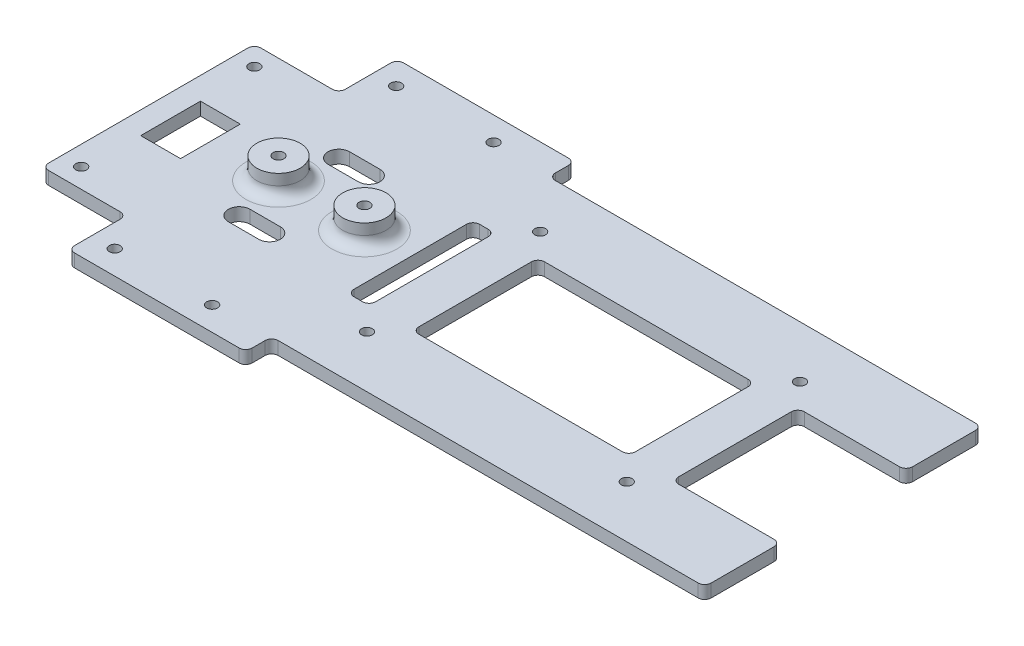
SolidWorks part; units mm, degrees
ref_plane "Front Plane" through (0, 0, 0) normal (0, 0, 1) x (1, 0, 0)
ref_plane "Top Plane" through (0, 0, 0) normal (0, 1, 0) x (1, 0, 0)
ref_plane "Right Plane" through (0, 0, 0) normal (1, 0, 0) x (0, 0, -1)
sketch "Sketch1" plane through (0, 0, 0) normal (0, 1, 0) x (1, 0, 0)
  line L1 (-20.5, -38) -> (20.5, -38)
  line L2 (20.5, -38) -> (20.5, -32)
  line L3 (20.5, -32) -> (120.5, -32)
  line L4 (120.5, -32) -> (120.5, 32)
  line L5 (120.5, 32) -> (20.5, 32)
  line L6 (20.5, 32) -> (20.5, 38)
  line L7 (20.5, 38) -> (-20.5, 38)
  line L8 (-20.5, -24.5) -> (-20.5, -38)
  line L21 (-20.5, 24.5) -> (-20.5, 38)
  line L24 (-40, 24.5) -> (-20.5, 24.5)
  line L26 (-40, 24.5) -> (-40, -24.5)
  line L27 (-40, -24.5) -> (-20.5, -24.5)
  line L28 (-35.5, -20) -> (-35.5, 20) construction
  line L29 (-31, -24.5) -> (-31, 24.5) construction
  circle A0 centre (-35.5, 20) radius 1.25
  circle A1 centre (-35.5, -20) radius 1.25
  point P2 (0, 38)
  point P3 (-40, 0)
  point P22 (-35.5, 0)
  dimension "D7" = 4.5
  dimension "D5" = 4.5
  dimension "D10" = 2.5
  dimension "D1" = 41
  dimension "D2" = 100
  dimension "D3" = 64
  dimension "D4" = 76
  dimension "D6" = 40
  dimension "D8" = 9
  dimension "D9" = 10.5
extrude "Boss-Extrude1" add sketch "Sketch1" along normal blind 3
sketch "Sketch2" plane through (0, 3, 0) normal (0, 1, 0) x (1, 0, 0)
  line L0 (9.925, 0) -> (-9.925, 0) construction
  line L1 (-9.925, 20) -> (-9.925, -20) construction
  line L2 (9.925, 20) -> (9.925, -20) construction
  circle A0 centre (-9.925, 20) radius 5
  circle A1 centre (9.925, 20) radius 5
  circle A2 centre (-9.925, 0) radius 5
  circle A3 centre (9.925, 0) radius 5
  circle A4 centre (9.925, -20) radius 5
  circle A5 centre (-9.925, -20) radius 5
  point P16 (0, 0)
  point P22 (-9.925, 0)
  point P23 (9.925, 0)
  dimension "D2" = 10
  dimension "D1" = 19.85
  dimension "D3" = 40
extrude "Boss-Extrude2" add sketch "Sketch2" along normal blind 5 contours A2 | A3
fillet "Fillet1" radius 2.5 2 edges at (9.925, 3, 5) (-9.925, 3, 5)
sketch "Sketch3" plane through (0, 0, 0) normal (0, -1, 0) x (-1, 0, 0)
  line L0 (9.925, 0) -> (-9.925, 0) construction
  line L1 (-90.5, 20) -> (-30.5, -20) construction
  line L2 (-30.5, 20) -> (-90.5, -20) construction
  line L3 (20.5, -38) -> (-20.5, -38) construction
  line L4 (-7.25, -32.5) -> (15.25, -32.5) construction
  line L7 (-7.25, 32.5) -> (15.25, 32.5) construction
  line L13 (-25.5, 14.5) -> (-20.5, 14.5)
  line L16 (-7.25, 32.5) -> (15.25, -32.5) construction
  line L17 (-25.5, 14.5) -> (-25.5, -14.5)
  line L18 (7.5, 11.5) -> (0.5, 11.5) construction
  line L19 (7.5, 9) -> (0.5, 9)
  line L20 (7.5, 14) -> (0.5, 14)
  line L21 (7.5, -11.5) -> (0.5, -11.5) construction
  line L22 (7.5, -14) -> (0.5, -14)
  line L23 (7.5, -9) -> (0.5, -9)
  line L24 (4, -11.5) -> (4, 11.5) construction
  line L25 (-25.5, -14.5) -> (-20.5, -14.5)
  line L26 (-20.5, 14.5) -> (-20.5, -14.5)
  line L27 (-25.5, 14.5) -> (-20.5, -14.5) construction
  line L28 (-25.5, -14.5) -> (-20.5, 14.5) construction
  line L29 (-120.5, -32) -> (-120.5, 32) construction
  line L30 (-20.5, 32) -> (-20.5, 38) construction
  line L31 (25.65, 6.9) -> (34.85, 6.9)
  line L32 (25.65, 6.9) -> (25.65, -6.9)
  line L33 (25.65, -6.9) -> (34.85, -6.9)
  line L34 (34.85, 6.9) -> (34.85, -6.9)
  line L35 (25.65, 6.9) -> (34.85, -6.9) construction
  line L36 (25.65, -6.9) -> (34.85, 6.9) construction
  line L37 (-120.5, 14.5) -> (-95.5, 14.5)
  line L38 (-120.5, 14.5) -> (-120.5, -14.5)
  line L39 (-120.5, -14.5) -> (-95.5, -14.5)
  line L40 (-95.5, 14.5) -> (-95.5, -14.5)
  line L41 (-120.5, 14.5) -> (-95.5, -14.5) construction
  line L42 (-120.5, -14.5) -> (-95.5, 14.5) construction
  line L43 (40, -24.5) -> (20.5, -24.5) construction
  line L44 (-85.5, 14.5) -> (-35.5, 14.5)
  line L46 (15.25, 32.5) -> (-7.25, -32.5) construction
  line L47 (-85.5, 14.5) -> (-85.5, -14.5)
  line L48 (-85.5, -14.5) -> (-35.5, -14.5)
  line L49 (-35.5, 14.5) -> (-35.5, -14.5)
  line L50 (-85.5, 14.5) -> (-35.5, -14.5) construction
  line L51 (-85.5, -14.5) -> (-35.5, 14.5) construction
  circle A2 centre (-30.5, -20) radius 1.25
  circle A3 centre (-90.5, -20) radius 1.25
  circle A4 centre (-30.5, 20) radius 1.25
  circle A5 centre (-90.5, 20) radius 1.25
  arc A14 (7.5, 9) -> (7.5, 14) centre (7.5, 11.5) ccw
  arc A15 (0.5, 14) -> (0.5, 9) centre (0.5, 11.5) ccw
  arc A16 (7.5, -14) -> (7.5, -9) centre (7.5, -11.5) ccw
  arc A17 (0.5, -9) -> (0.5, -14) centre (0.5, -11.5) ccw
  circle A18 centre (-7.25, 32.5) radius 1.25
  circle A19 centre (15.25, 32.5) radius 1.25
  circle A20 centre (-9.925, 0) radius 1.25
  circle A21 centre (9.925, 0) radius 1.25
  circle A22 centre (15.25, -32.5) radius 1.25
  circle A23 centre (-7.25, -32.5) radius 1.25
  point P8 (0, 0)
  point P16 (-60.5, 0)
  point P17 (-60.5, 0)
  point P25 (4, -32.5)
  point P26 (4, 32.5)
  point P28 (4, 0)
  point P29 (4, 0)
  point P30 (4, 0)
  point P33 (-23, 0)
  point P34 (0, 0)
  point P47 (4, 11.5)
  point P53 (0, 0)
  point P54 (0, 0)
  point P62 (4, -11.5)
  point P69 (10, -11.5)
  point P70 (-2, -11.5)
  point P75 (0, 0)
  point P89 (30.25, 0)
  point P93 (-29.25, 20)
  point P95 (-108, 0)
  point P102 (30.25, -24.5)
  point P104 (0, 0)
  point P108 (-60.5, 0)
  dimension "D2" = 2.5
  dimension "D3" = 40
  dimension "D5" = 2.5
  dimension "D9" = 5.5
  dimension "D7" = 2.5
  dimension "D4" = 60
  dimension "D6" = 10
  dimension "D8" = 22.5
  dimension "D10" = 4
  dimension "D11" = 5
  dimension "D12" = 13.8
  dimension "D13" = 28
  dimension "D14" = 12
  dimension "D15" = 9.2
  dimension "D16" = 19.85
  dimension "D17" = 29
  dimension "D18" = 5
  dimension "D20" = 5
  dimension "D21" = 5
  dimension "D22" = 5
  dimension "D23" = 5
extrude "Cut-Extrude1" cut sketch "Sketch3" against normal through all contours L49 L44 L47 L48 | L40 L37 L38 L39 | L23 A17 L22 A16 | L20 A15 L19 A14 | A4 | A5 | A3 | A2 | A23 | A22 | L34 L31 L32 L33 | A21 | A20 | A18 | A19 | L17 L13 L26 L25 region at (-4, 0, -11.5) region at (-4, 0, 11.5) region at (-30.25, 0, 0) region at (108, 0, 0) region at (60.5, 0, 0) region at (30.5, 0, 20) region at (90.5, 0, 20) region at (30.5, 0, -20) region at (90.5, 0, -20) region at (7.25, 0, -32.5) region at (-15.25, 0, -32.5) region at (9.925, 0, 0) region at (-9.925, 0, 0) region at (-15.25, 0, 32.5) region at (7.25, 0, 32.5)
fillet "Fillet2" radius 1.5 24 edges at (120.5, 1.5, -32) (120.5, 1.5, 32) (20.5, 1.5, -32) (20.5, 1.5, 32) (20.5, 1.5, 38) (-20.5, 1.5, 38) (20.5, 1.5, -38) (-40, 1.5, 24.5) (-20.5, 1.5, -24.5) (-20.5, 1.5, 24.5) (-20.5, 1.5, -38) (-40, 1.5, -24.5) (95.5, 1.5, 14.5) (95.5, 1.5, -14.5) (35.5, 1.5, -14.5) (85.5, 1.5, -14.5) (85.5, 1.5, 14.5) (35.5, 1.5, 14.5) (20.5, 1.5, 14.5) (25.5, 1.5, 14.5) (20.5, 1.5, -14.5) (25.5, 1.5, -14.5) (120.5, 1.5, 14.5) (120.5, 1.5, -14.5)
